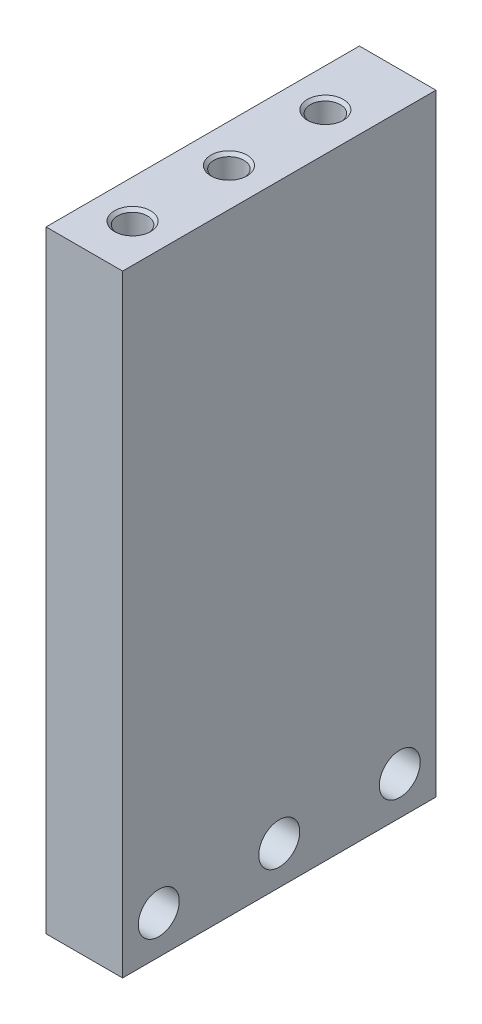
SolidWorks part; units mm, degrees
ref_plane "Front Plane" through (0, 0, 0) normal (0, 0, 1) x (1, 0, 0)
ref_plane "Top Plane" through (0, 0, 0) normal (0, 1, 0) x (1, 0, 0)
ref_plane "Right Plane" through (0, 0, 0) normal (1, 0, 0) x (0, 0, -1)
sketch "Sketch1" plane through (0, 0, 0) normal (0, 0, 1) x (1, 0, 0)
  line L1 (0, 0) -> (6.35, 0)
  line L2 (0, 0) -> (0, 50.8)
  line L3 (0, 50.8) -> (6.35, 50.8)
  line L4 (6.35, 0) -> (6.35, 50.8)
extrude "Boss-Extrude1" add sketch "Sketch1" along normal blind 26
sketch "Sketch4" plane through (6.35, 0, 0) normal (1, 0, 0) x (0, 0, -1)
  line L0 (0, 0) -> (0, 50.8) construction
  line L1 (-26, 0) -> (-26, 50.8) construction
  line L2 (-26, 0) -> (0, 0) construction
  circle A0 centre (-3, 3.175) radius 1.7
  circle A1 centre (-23, 3.175) radius 1.7
  circle A2 centre (-13, 3.175) radius 1.7
  dimension "D2" = 3.4
  dimension "D3" = 3
  dimension "D4" = 3
  dimension "D5" = 3.175
  dimension "D6" = 3.175
extrude "Cut-Extrude3" cut sketch "Sketch4" against normal blind 6.35
sketch "Sketch6" plane through (0, 0, 0) normal (-1, 0, 0) x (0, 0, 1)
  line L0 (26, 0) -> (0, 0) construction
  circle A0 centre (13, 3.175) radius 1.5
  circle A1 centre (3, 3.175) radius 1.7 construction
  dimension "D1" = 3
  dimension "D2" = 10
  dimension "D3" = 3.175
sketch "Sketch9" plane through (0, 50.8, 0) normal (0, 1, 0) x (1, 0, 0)
  circle A6 centre (3.175, -6) radius 1.25
  circle A7 centre (3.175, -14) radius 1.25
  circle A8 centre (3.175, -22) radius 1.25
sketch "Sketch12" plane through (0, 50.8, 0) normal (0, 1, 0) x (1, 0, 0)
  circle A0 centre (3.175, -6) radius 1.25
  circle A1 centre (3.175, -14) radius 1.25
  circle A2 centre (3.175, -22) radius 1.25
  dimension "D1" = 2.5
  dimension "D2" = 2.5
  dimension "D3" = 2.5
sketch "Sketch14" plane through (0, 50.8, 0) normal (0, 1, 0) x (1, 0, 0)
  circle A0 centre (3.175, -22) radius 1.25 construction
  circle A1 centre (3.175, -14) radius 1.25 construction
  circle A2 centre (3.175, -6) radius 1.25 construction
  circle A3 centre (3.175, -22) radius 1.25
  circle A4 centre (3.175, -14) radius 1.25
  circle A5 centre (3.175, -6) radius 1.25
extrude "Cut-Extrude13" cut sketch "Sketch14" against normal blind 5
chamfer "Chamfer3" distance 0.25 angle 45 3 edges at (3.175, 50.8, 23.25) (3.175, 50.8, 15.25) (3.175, 50.8, 7.25)
